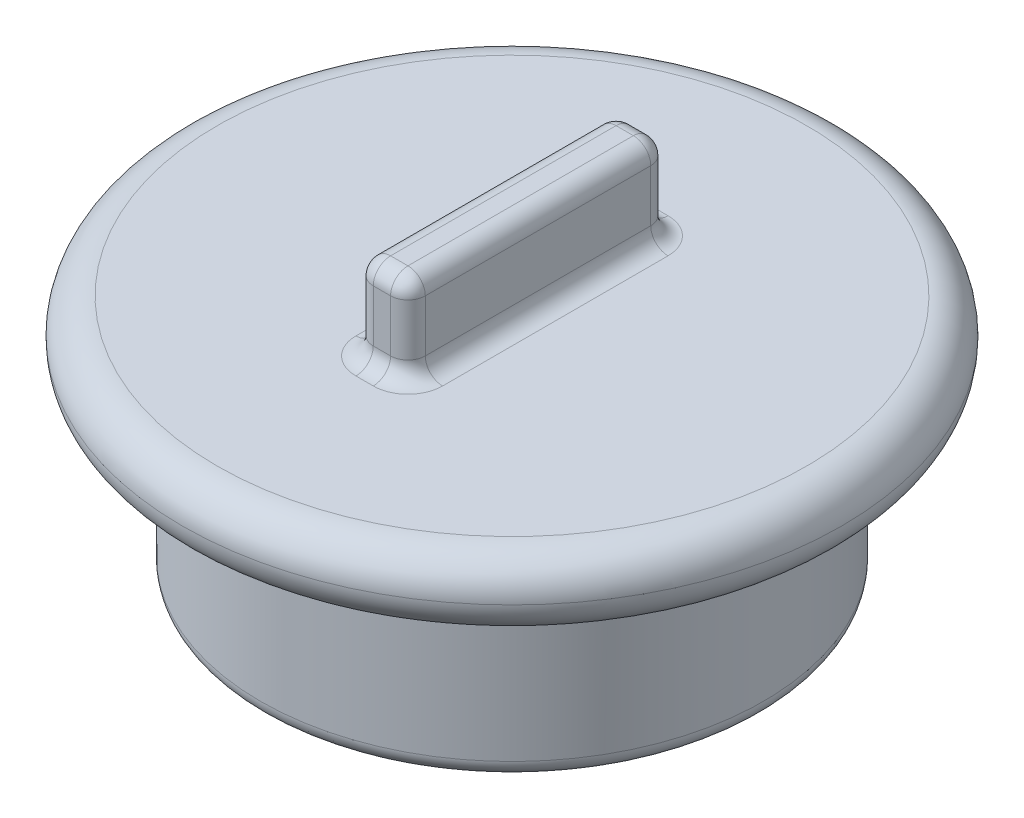
SolidWorks part; units mm, degrees
ref_plane "前基準面" through (0, 0, 0) normal (0, 0, 1) x (1, 0, 0)
ref_plane "上基準面" through (0, 0, 0) normal (0, 1, 0) x (1, 0, 0)
ref_plane "右基準面" through (0, 0, 0) normal (1, 0, 0) x (0, 0, -1)
sketch "草圖1" plane through (0, 0, 0) normal (0, 1, 0) x (1, 0, 0)
  circle A0 centre (0, 0) radius 19
  dimension "D1" = 38
extrude "填料-伸長1" add sketch "草圖1" along normal blind 4
sketch "草圖2" plane through (0, 4, 0) normal (0, 1, 0) x (1, 0, 0)
  line L1 (-1.5, 7.5) -> (1.5, 7.5)
  line L2 (-1.5, 7.5) -> (-1.5, -7.5)
  line L3 (-1.5, -7.5) -> (1.5, -7.5)
  line L4 (1.5, 7.5) -> (1.5, -7.5)
  circle A0 centre (0, 0) radius 19 construction
  dimension "D1" = 3
  dimension "D2" = 15
  dimension "D3" = 1.5
  dimension "D4" = 7.5
extrude "填料-伸長2" add sketch "草圖2" along normal blind 5
fillet "圓角1" radius 1 12 edges at (-1.5, 9, 0) (1.5, 9, 0) (1.5, 4, 0) (-1.5, 4, 0) (-1.5, 6.5, 7.5) (0, 9, 7.5) (1.5, 6.5, 7.5) (0, 4, 7.5) (1.5, 6.5, -7.5) (0, 9, -7.5) (-1.5, 6.5, -7.5) (0, 4, -7.5)
fillet "圓角3" radius 2 2 edges at (0, 0, 19) (0, 4, 19)
sketch "草圖3" plane through (0, 0, 0) normal (0, -1, 0) x (1, 0, 0)
  circle A0 centre (0, 0) radius 14.5
  circle A1 centre (0, 0) radius 12.5
  dimension "D1" = 29
  dimension "D2" = 2
extrude "填料-伸長3" add sketch "草圖3" along normal blind 10
fillet "圓角4" radius 1 2 edges at (0, -10, -12.5) (0, -10, -14.5)
